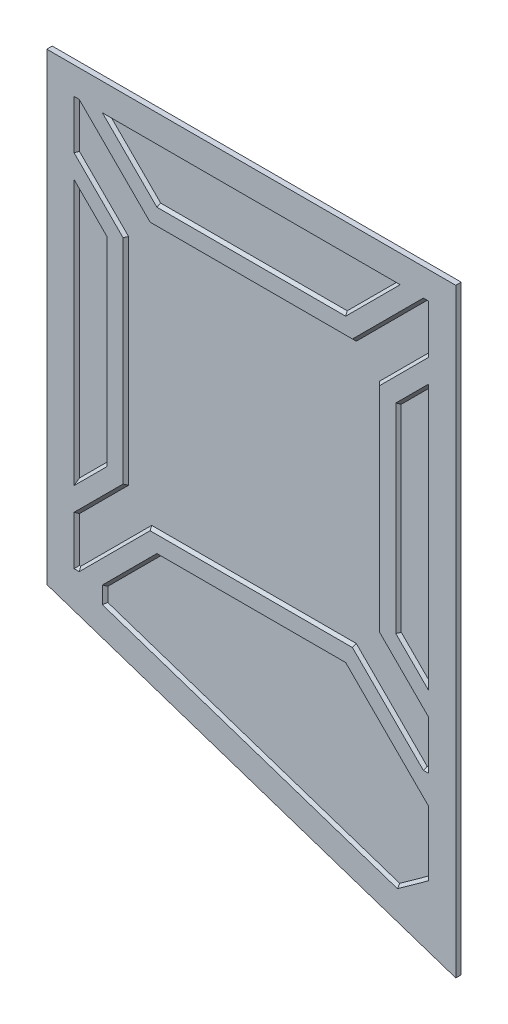
SolidWorks part; units mm, degrees
ref_plane "Plan de face" through (0, 0, 0) normal (0, 0, 1) x (1, 0, 0)
ref_plane "Plan de dessus" through (0, 0, 0) normal (0, 1, 0) x (1, 0, 0)
ref_plane "Plan de droite" through (0, 0, 0) normal (1, 0, 0) x (0, 0, -1)
sketch "Esquisse1" plane through (0, 0, 0) normal (0, 0, 1) x (1, 0, 0)
  line L0 (750, 0) -> (0, -250)
  line L1 (0, 0) -> (750, 0) construction
  line L2 (0, 0) -> (0, 850)
  line L3 (0, 850) -> (750, 850)
  line L4 (750, 0) -> (750, 850)
  line L5 (0, -250) -> (0, 0)
  dimension "D1" = 850
  dimension "D2" = 750
  dimension "D3" = 1100
extrude "Boss.-Extru.1" add sketch "Esquisse1" along normal blind 10
sketch "Esquisse2" plane through (0, 0, 10) normal (0, 0, 1) x (1, 0, 0)
  line L0 (189.4975, 670) -> (140, 620.5025) construction
  line L1 (110, 241.9239) -> (110, 608.0761)
  line L2 (110, 608.0761) -> (50, 668.0761)
  line L3 (201.9239, 700) -> (548.0761, 700)
  line L4 (375, 850) -> (375, -125) construction
  line L5 (750, 850) -> (0, 850) construction
  line L6 (50, 800) -> (50, 710.5025)
  line L7 (50, 710.5025) -> (140, 620.5025)
  line L8 (0, -250) -> (750, 0) construction
  line L9 (750, 425) -> (0, 425) construction
  line L10 (750, 0) -> (750, 850) construction
  line L11 (0, 850) -> (0, -250) construction
  line L12 (50, 800) -> (50, 50) construction
  line L13 (610, 670) -> (560.5025, 670) construction
  line L14 (610, 620.5025) -> (610, 670) construction
  line L15 (700, 800) -> (50, 800) construction
  line L16 (140, 620.5025) -> (140, 229.4975)
  line L17 (50, 800) -> (59.4975, 800)
  line L18 (59.4975, 800) -> (189.4975, 670)
  line L19 (560.5025, 670) -> (189.4975, 670)
  line L20 (648.0761, 800) -> (101.9239, 800)
  line L21 (101.9239, 800) -> (201.9239, 700)
  line L22 (700, 800) -> (700, 50) construction
  line L23 (50, 668.0761) -> (50, 181.9239)
  line L24 (560.5025, 670) -> (610, 620.5025) construction
  line L25 (140, 620.5025) -> (140, 670) construction
  line L26 (140, 670) -> (189.4975, 670) construction
  line L27 (700, 668.0761) -> (700, 181.9239)
  line L28 (648.0761, 800) -> (548.0761, 700)
  line L29 (690.5025, 800) -> (560.5025, 670)
  line L30 (700, 800) -> (690.5025, 800)
  line L31 (610, 620.5025) -> (610, 229.4975)
  line L32 (700, 710.5025) -> (610, 620.5025)
  line L33 (700, 800) -> (700, 710.5025)
  line L34 (640, 608.0761) -> (700, 668.0761)
  line L35 (640, 241.9239) -> (640, 608.0761)
  line L36 (140, 180) -> (189.4975, 180) construction
  line L37 (140, 229.4975) -> (140, 180) construction
  line L38 (560.5025, 180) -> (610, 229.4975) construction
  line L39 (700, 50) -> (50, 50) construction
  line L40 (610, 229.4975) -> (610, 180) construction
  line L41 (610, 180) -> (560.5025, 180) construction
  line L42 (189.4975, 180) -> (140, 229.4975) construction
  line L43 (640, 241.9239) -> (700, 181.9239)
  line L44 (700, 50) -> (700, 139.4975)
  line L45 (700, 139.4975) -> (610, 229.4975)
  line L46 (700, 50) -> (690.5025, 50)
  line L47 (690.5025, 50) -> (560.5025, 180)
  line L48 (648.0761, 50) -> (548.0761, 150)
  line L49 (101.9239, 50) -> (201.9239, 150)
  line L50 (648.0761, 50) -> (101.9239, 50) construction
  line L51 (560.5025, 180) -> (189.4975, 180)
  line L52 (59.4975, 50) -> (189.4975, 180)
  line L53 (50, 50) -> (59.4975, 50)
  line L54 (50, 139.4975) -> (140, 229.4975)
  line L55 (50, 50) -> (50, 139.4975)
  line L56 (201.9239, 150) -> (548.0761, 150)
  line L57 (110, 241.9239) -> (50, 181.9239)
  line L58 (101.9239, 50) -> (50, -1.9239)
  line L59 (50, -1.9239) -> (50, -120.6287)
  line L60 (106.921, -161.655) -> (648.0761, 18.73)
  line L61 (648.0761, 18.73) -> (648.0761, 50)
  line L62 (50, -120.6287) -> (106.921, -161.655)
  point P5 (375, 180)
  point P20 (375, 670)
  point P23 (590, 425)
  point P29 (375, 670)
  point P31 (375, 700)
  point P32 (375, 800)
  point P33 (110, 425)
  point P34 (140, 425)
  point P37 (375, 700)
  point P39 (610, 425)
  point P40 (375, 700)
  point P41 (375, 670)
  point P47 (620, 425)
  point P59 (640, 425)
  point P61 (610, 425)
  point P64 (700, 425)
  point P65 (50, 425)
  point P68 (140, 425)
  point P70 (110, 425)
  point P71 (375, 150)
  point P72 (610, 425)
  point P73 (140, 425)
  point P74 (375, 50)
  point P77 (50, -180.6287)
  dimension "D2" = 90
  dimension "D3" = 130
  dimension "D4" = 70
  dimension "D5" = 45
  dimension "D6" = 30
  dimension "D7" = 30
  dimension "D8" = 30
  dimension "D9" = 30
  dimension "D1" = 50
  dimension "D10" = 50
  dimension "D11" = 50
  dimension "D12" = 50
extrude "Enlèv. mat.-Extru.1" cut sketch "Esquisse2" against normal blind 5
chamfer "Chanfrein1" distance 5 angle 45 39 edges at (50, 425, 5) (80, 638.0761, 5) (124.4975, 735, 5) (375, 670, 5) (140, 425, 5) (95, 665.5025, 5) (50, 755.2513, 5) (54.7487, 800, 5) (375, 800, 5) (375, 700, 5) (151.9239, 750, 5) (110, 425, 5) (80, 211.9239, 5) (625.5025, 735, 5) (695.2513, 800, 5) (700, 755.2513, 5) (655, 665.5025, 5) (610, 425, 5) (655, 184.4975, 5) (700, 94.7487, 5) (695.2513, 50, 5) (625.5025, 115, 5) (375, 180, 5) (124.4975, 115, 5) (54.7487, 50, 5) (50, 94.7487, 5) (95, 184.4975, 5) (598.0761, 750, 5) (700, 425, 5) (670, 211.9239, 5) (640, 425, 5) (670, 638.0761, 5) (375, 150, 5) (598.0761, 100, 5) (648.0761, 34.365, 5) (377.4986, -71.4625, 5) (78.4605, -141.1419, 5) (50, -61.2763, 5) (125.9619, 74.0381, 5)
mirror "Symétrie1" about plane through (750, 0, 10) normal (-1, 0, 0) of bodies 102
sketch "Esquisse3" plane through (0, 850, 0) normal (0, 1, 0) x (1, 0, 0)
  line L1 (0, -10) -> (750, -10)
  line L2 (0, -10) -> (0, 0)
  line L3 (0, 0) -> (750, 0)
  line L4 (750, -10) -> (750, 0)
extrude "Enlèv. mat.-Extru.2" cut sketch "Esquisse3" against normal through all
